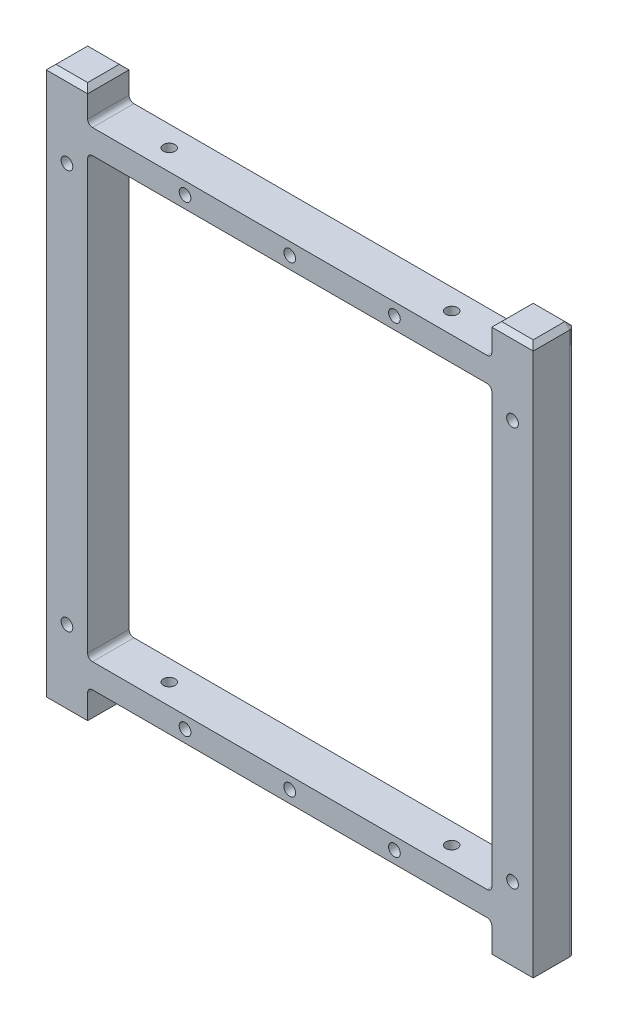
SolidWorks part; units mm, degrees
material "6061 Alloy"
ref_plane "Frontal" through (0, 0, 0) normal (0, 0, 1) x (1, 0, 0)
ref_plane "Superior" through (0, 0, 0) normal (0, 1, 0) x (1, 0, 0)
ref_plane "Direito" through (0, 0, 0) normal (1, 0, 0) x (0, 0, -1)
sketch "Sketch1" plane through (0, 0, 0) normal (0, 0, 1) x (1, 0, 0)
  line L1 (-50, -56.75) -> (50, -56.75)
  line L2 (-50, -56.75) -> (-50, 56.75)
  line L3 (-50, 56.75) -> (50, 56.75)
  line L4 (50, -56.75) -> (50, 56.75)
  line L5 (-50, -56.75) -> (50, 56.75) construction
  line L6 (-50, 56.75) -> (50, -56.75) construction
  point P0 (0, 0)
  dimension "D1" = 113.5
  dimension "D2" = 100
extrude "Boss-Extrude1" add sketch "Sketch1" along normal mid plane 8.5
sketch "Sketch4" plane through (0, 0, 4.25) normal (0, 0, 1) x (1, 0, 0)
  line L0 (-50, 56.75) -> (-50, -56.75) construction
  line L1 (-40.5, -44.75) -> (40.5, -44.75)
  line L2 (-41.5, -43.75) -> (-41.5, 44.25)
  line L3 (-40.5, 45.25) -> (40.5, 45.25)
  line L4 (41.5, -43.75) -> (41.5, 44.25)
  line L5 (-40.5, -43.75) -> (40.5, 44.25) construction
  line L6 (-40.5, 44.25) -> (40.5, -43.75) construction
  line L7 (50, 56.75) -> (-50, 56.75) construction
  line L8 (-41.5, 56.75) -> (41.5, 56.75)
  line L9 (-41.5, 56.75) -> (-41.5, 51.25)
  line L10 (-40.5, 50.25) -> (40.5, 50.25)
  line L11 (41.5, 56.75) -> (41.5, 51.25)
  line L12 (-50, -56.75) -> (50, -56.75) construction
  line L13 (-41.5, -56.75) -> (41.5, -56.75)
  line L14 (-41.5, -56.75) -> (-41.5, -50.75)
  line L15 (-40.5, -49.75) -> (40.5, -49.75)
  line L16 (41.5, -56.75) -> (41.5, -50.75)
  line L17 (50, -56.75) -> (50, 56.75) construction
  arc A0 (-41.5, 51.25) -> (-40.5, 50.25) centre (-40.5, 51.25) ccw
  arc A1 (40.5, 50.25) -> (41.5, 51.25) centre (40.5, 51.25) ccw
  arc A2 (-40.5, 45.25) -> (-41.5, 44.25) centre (-40.5, 44.25) ccw
  arc A3 (40.5, 45.25) -> (41.5, 44.25) centre (40.5, 44.25) cw
  arc A4 (41.5, -43.75) -> (40.5, -44.75) centre (40.5, -43.75) cw
  arc A5 (-40.5, -44.75) -> (-41.5, -43.75) centre (-40.5, -43.75) cw
  arc A6 (-40.5, -49.75) -> (-41.5, -50.75) centre (-40.5, -50.75) ccw
  arc A7 (40.5, -49.75) -> (41.5, -50.75) centre (40.5, -50.75) cw
  point P0 (1.8681, -1.8902)
  dimension "D11" = 1
  dimension "D12" = 1
  dimension "D13" = 1
  dimension "D14" = 1
  dimension "D15" = 1
  dimension "D16" = 1
  dimension "D17" = 1
  dimension "D18" = 1
  dimension "D1" = 8.5
  dimension "D2" = 8.5
  dimension "D3" = 8.5
  dimension "D4" = 6.5
  dimension "D5" = 8.5
  dimension "D6" = 8.5
  dimension "D7" = 7
  dimension "D8" = 5
  dimension "D9" = 5
  dimension "D10" = 8.5
extrude "Cut-Extrude1" cut sketch "Sketch4" against normal through all
hole_wizard "M2 Hole1-C" positions "Sketch6" profile "Sketch5" hole size "M2" standard "DIN"
sketch "Sketch6" plane through (0, 0, 4.25) normal (0, 0, 1) x (1, 0, 0)
  line L0 (-50, 56.75) -> (-50, -56.75) construction
  line L1 (50, -56.75) -> (50, 56.75) construction
  line L2 (-40.5, 50.25) -> (40.5, 50.25) construction
  line L3 (40.5, -49.75) -> (-40.5, -49.75) construction
  point P0 (-45.75, -40.75)
  point P2 (45.75, -40.75)
  point P4 (-45.75, 41.25)
  point P6 (45.75, 41.25)
  dimension "D1" = 4.25
  dimension "D2" = 4.25
  dimension "D3" = 9
  dimension "D4" = 9
sketch "Sketch5" plane through (-45.75, -40.75, 4.25) normal (1, 0, 0) x (0, -1, 0)
  line L0 (0, 0) -> (0, 3.721)
  line L1 (0, 3.721) -> (1.2, 3)
  line L2 (1.2, 3) -> (1.2, 0)
  line L5 (1.2, 0) -> (0, 0)
  line L10 (0, 3.721) -> (-1.2, 3) construction
  line L11 (0, -6.35) -> (0, 107.95) construction
  dimension "Hole Dia." = 2.4
  dimension "Hole Depth" = 3
  dimension "Drill Angle" = 118
hole_wizard "M2 Hole2-D" positions "Sketch26" profile "Sketch24" hole size "M2" standard "DIN"
sketch "Sketch26" plane through (0, 0, 4.25) normal (0, 0, 1) x (1, 0, 0)
  line L0 (40.5, 45.25) -> (-40.5, 45.25) construction
  line L1 (-50, 56.75) -> (-50, -56.75) construction
  line L2 (50, -56.75) -> (50, 56.75) construction
  line L3 (-40.5, -44.75) -> (40.5, -44.75) construction
  point P0 (-21.5, 47.75)
  point P2 (21.5, 47.75)
  point P4 (-21.5, -47.25)
  point P6 (21.5, -47.25)
  dimension "D1" = 2.5
  dimension "D2" = 28.5
  dimension "D3" = 28.5
  dimension "D4" = 2.5
sketch "Sketch24" plane through (-21.5, 47.75, 4.25) normal (1, 0, 0) x (0, -1, 0)
  line L0 (0, 0) -> (0, 5.721)
  line L1 (0, 5.721) -> (1.2, 5)
  line L2 (1.2, 5) -> (1.2, 0)
  line L5 (1.2, 0) -> (0, 0)
  line L10 (0, 5.721) -> (-1.2, 5) construction
  line L11 (0, -6.35) -> (0, 107.95) construction
  dimension "Hole Dia." = 2.4
  dimension "Hole Depth" = 5
  dimension "Drill Angle" = 118
hole_wizard "M2 Hole3-E" positions "Sketch13" profile "Sketch12" hole size "M2" standard "DIN"
sketch "Sketch13" plane through (0, 0, 4.25) normal (0, 0, 1) x (1, 0, 0)
  line L0 (40.5, -49.75) -> (-40.5, -49.75) construction
  line L1 (-40.5, 50.25) -> (40.5, 50.25) construction
  point P0 (0, 47.75)
  point P2 (0, -47.25)
  dimension "D1" = 2.5
  dimension "D2" = 2.5
sketch "Sketch12" plane through (0, 47.75, 4.25) normal (1, 0, 0) x (0, -1, 0)
  line L0 (0, 0) -> (0, 4.721)
  line L1 (0, 4.721) -> (1.2, 4)
  line L2 (1.2, 4) -> (1.2, 0)
  line L5 (1.2, 0) -> (0, 0)
  line L10 (0, 4.721) -> (-1.2, 4) construction
  line L11 (0, -6.35) -> (0, 107.95) construction
  dimension "Hole Dia." = 2.4
  dimension "Hole Depth" = 4
  dimension "Drill Angle" = 118
hole_wizard "M2 Hole4-F" positions "Sketch23" profile "Sketch22" hole size "M2" standard "DIN"
sketch "Sketch23" plane through (0, 50.25, 0) normal (0, 1, 0) x (1, 0, 0)
  line L0 (-40.5, 4.25) -> (40.5, 4.25) construction
  line L1 (-41.5, 4.25) -> (-41.5, -4.25) construction
  line L2 (41.5, 4.25) -> (41.5, -4.25) construction
  point P0 (-29, 0)
  point P2 (29, 0)
  dimension "D1" = 4.25
  dimension "D2" = 12.5
  dimension "D3" = 12.5
sketch "Sketch22" plane through (-29, 50.25, 0) normal (1, 0, 0) x (0, 0, 1)
  line L0 (0, 0) -> (0, 10.721)
  line L1 (0, 10.721) -> (1.2, 10)
  line L2 (1.2, 10) -> (1.2, 0)
  line L5 (1.2, 0) -> (0, 0)
  line L10 (0, 10.721) -> (-1.2, 10) construction
  line L11 (0, -6.35) -> (0, 107.95) construction
  dimension "Hole Dia." = 2.4
  dimension "Hole Depth" = 10
  dimension "Drill Angle" = 118
hole_wizard "M2 Hole5-G" positions "Sketch17" profile "Sketch16" hole size "M2" standard "DIN"
sketch "Sketch17" plane through (0, -49.75, 0) normal (0, -1, 0) x (-1, 0, 0)
  line L0 (41.5, 4.25) -> (41.5, -4.25) construction
  line L1 (-41.5, 4.25) -> (-41.5, -4.25) construction
  line L2 (-40.5, -4.25) -> (40.5, -4.25) construction
  point P0 (29, 0)
  point P2 (-29, 0)
  dimension "D1" = 12.5
  dimension "D2" = 12.5
  dimension "D3" = 4.25
sketch "Sketch16" plane through (-29, -49.75, 0) normal (1, 0, 0) x (0, 0, -1)
  line L0 (0, 0) -> (0, 10.721)
  line L1 (0, 10.721) -> (1.2, 10)
  line L2 (1.2, 10) -> (1.2, 0)
  line L5 (1.2, 0) -> (0, 0)
  line L10 (0, 10.721) -> (-1.2, 10) construction
  line L11 (0, -6.35) -> (0, 107.95) construction
  dimension "Hole Dia." = 2.4
  dimension "Hole Depth" = 10
  dimension "Drill Angle" = 118
hole_wizard "M2 Hole6-H" positions "Sketch21" profile "Sketch20" hole size "M2" standard "DIN"
sketch "Sketch21" plane through (0, 0, -4.25) normal (0, 0, -1) x (-1, 0, 0)
  line L0 (40.5, 50.25) -> (-40.5, 50.25) construction
  line L1 (-41.5, 51.25) -> (-41.5, 56.75) construction
  line L2 (41.5, 56.75) -> (41.5, 51.25) construction
  line L3 (-40.5, -49.75) -> (40.5, -49.75) construction
  point P0 (-35.5, 47.75)
  point P2 (35.5, 47.75)
  point P4 (-35.5, -47.25)
  point P6 (35.5, -47.25)
  dimension "D1" = 2.5
  dimension "D2" = 6
  dimension "D3" = 6
  dimension "D4" = 2.5
sketch "Sketch20" plane through (35.5, 47.75, -4.25) normal (1, 0, 0) x (0, 1, 0)
  line L0 (0, 0) -> (0, 5.721)
  line L1 (0, 5.721) -> (1.2, 5)
  line L2 (1.2, 5) -> (1.2, 0)
  line L5 (1.2, 0) -> (0, 0)
  line L10 (0, 5.721) -> (-1.2, 5) construction
  line L11 (0, -6.35) -> (0, 107.95) construction
  dimension "Hole Dia." = 2.4
  dimension "Hole Depth" = 5
  dimension "Drill Angle" = 118
fillet "Fillet1" radius 1 2 edges at (-50, 0, -4.25) (50, 0, -4.25)
chamfer "Chamfer1" distance 1 angle 45 20 edges at (-41.5, -56.75, 0) (-45.75, -56.75, 4.25) (-50, -56.75, 0.5) (-49.7071, -56.75, -3.9571) (-45.25, -56.75, -4.25) (-45.75, 56.75, 4.25) (-50, 56.75, 0.5) (-49.7071, 56.75, -3.9571) (-45.25, 56.75, -4.25) (-41.5, 56.75, 0) (45.75, -56.75, 4.25) (41.5, -56.75, 0) (45.25, -56.75, -4.25) (49.7071, -56.75, -3.9571) (50, -56.75, 0.5) (49.7071, 56.75, -3.9571) (50, 56.75, 0.5) (45.75, 56.75, 4.25) (41.5, 56.75, 0) (45.25, 56.75, -4.25)
